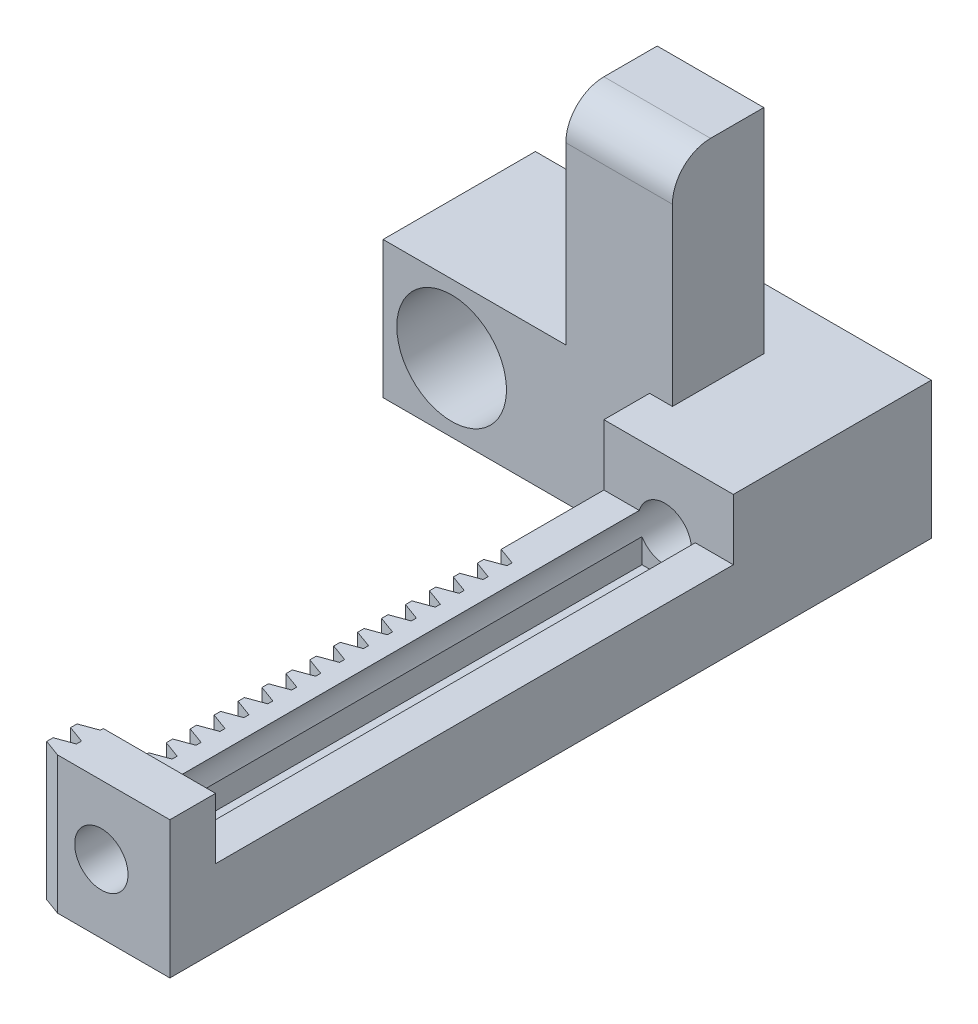
SolidWorks part; units mm, degrees
ref_plane "前视基准面" through (0, 0, 0) normal (0, 0, 1) x (1, 0, 0)
ref_plane "上视基准面" through (0, 0, 0) normal (0, 1, 0) x (1, 0, 0)
ref_plane "右视基准面" through (0, 0, 0) normal (1, 0, 0) x (0, 0, -1)
other "Configuration Table"
sketch "草图1" plane through (0, 0, 0) normal (0, 0, 1) x (1, 0, 0)
  line L1 (-13, 4.5) -> (13, 4.5)
  line L2 (-13, 4.5) -> (-13, -4.5)
  line L3 (-13, -4.5) -> (13, -4.5)
  line L4 (13, 4.5) -> (13, -4.5)
  line L5 (-13, 4.5) -> (13, -4.5) construction
  line L6 (-13, -4.5) -> (13, 4.5) construction
  point P0 (0, 0)
  dimension "D1" = 26
  dimension "D2" = 9
extrude "凸台-拉伸1" add sketch "草图1" against normal blind 10
sketch "草图2" plane through (0, 0, 0) normal (0, 0, 1) x (1, 0, 0)
  line L0 (0, 8.6502) -> (0, -9.0329) construction
  line L1 (8.5, 8.6502) -> (8.5, -9.0329) construction
  line L5 (-13, 0) -> (13, 0)
  line L6 (-13, 0) -> (13, 0) construction
  circle A0 centre (8.5, 0) radius 3.6
  circle A2 centre (-8.5, 0) radius 3.6
  dimension "D4" = 7.2
  dimension "D1" = 8.5
  dimension "D3" = 4.5
extrude "切除-拉伸1" cut sketch "草图2" against normal through all
sketch "草图5" plane through (-13, 0, 0) normal (-1, 0, 0) x (0, 0, 1)
  line L0 (0, 4.5) -> (-10, 4.5)
  line L1 (-10, 4.5) -> (-10, 8.3014)
  line L2 (-10, 8.3014) -> (-10, 30.5)
  line L3 (-9, 31.5) -> (-8, 31.5)
  line L4 (-8, 31.5) -> (-8, 20.1)
  line L5 (-6.4, 18.5) -> (-2.5, 18.5)
  line L6 (0, 16) -> (0, 4.5)
  line L7 (-10, 4.5) -> (-10, -4.5) construction
  arc A0 (-9, 31.5) -> (-10, 30.5) centre (-9, 30.5) ccw
  arc A1 (-6.4, 18.5) -> (-8, 20.1) centre (-6.4, 20.1) cw
  arc A2 (0, 16) -> (-2.5, 18.5) centre (-2.5, 16) ccw
  dimension "D4" = 1
  dimension "D5" = 1.6
  dimension "D6" = 2.5
  dimension "D1" = 27
  dimension "D2" = 14
  dimension "D3" = 8
extrude "凸台-拉伸2" add sketch "草图5" against normal through all
extrude "切除-拉伸2" cut sketch "草图5<2>" against normal blind 7
sketch "草图5<2>" plane through (-13, 0, 0) normal (-1, 0, 0) x (0, 0, 1) same geometry as "草图5"
mirror "镜向1" about plane through (0, 0, 0) normal (1, 0, 0) of "切除-拉伸2"
sketch "草图7" plane through (0, 0, 0) normal (0, 0, 1) x (1, 0, 0)
  line L0 (0, -9.5936) -> (0, 36.1115) construction
  line L2 (4.5, -4.5) -> (4.5, 4.5)
  line L3 (13, 4.5) -> (4.5, 4.5)
  line L4 (13, 4.5) -> (13, -4.5)
  line L5 (13, -4.5) -> (4.5, -4.5)
  line L6 (-13, -4.5) -> (13, -4.5) construction
  line L8 (4.5, -9.5936) -> (4.5, 36.1115) construction
  dimension "D1" = 4.5
extrude "凸台-拉伸3" add sketch "草图7" along normal blind 40
sketch "草图8" plane through (0, 0, 40) normal (0, 0, 1) x (1, 0, 0)
  circle A0 centre (8.5, 0) radius 1.75
  dimension "D1" = 3.5
extrude "切除-拉伸3" cut sketch "草图8" against normal blind 40
sketch "草图9" plane through (0, 4.5, 0) normal (0, 1, 0) x (1, 0, 0)
  line L2 (13, -40) -> (4.5, -40) construction
  line L3 (7, -3) -> (10.5, -3)
  line L5 (6, 10) -> (13, 10) construction
  line L6 (7, -37) -> (10.5, -37)
  line L7 (10.5, 10) -> (10.5, -40)
  line L8 (10.5, -3) -> (10.5, -37)
  line L11 (7, -40) -> (7, 0)
  line L12 (7, -37) -> (7, -3)
  dimension "D1" = 3
  dimension "D2" = 13
  dimension "D3" = 2.5
  dimension "D4" = 2.5
extrude "切除-拉伸4" cut sketch "草图9" against normal blind 7
sketch "草图10" plane through (0, 4.5, 0) normal (0, 1, 0) x (1, 0, 0)
  line L8 (5.625, -40) -> (5.625, -40.3304)
  line L9 (5.625, -40.3304) -> (4.5, -40.7399)
  line L10 (4.5, -40.7399) -> (4.5, -39.5905)
  line L11 (4.5, -39.5905) -> (5.625, -40)
  line L12 (5.625, -40.1652) -> (4.5, -40.1652) construction
  line L13 (5, -39.7725) -> (5, -40.5579) construction
  line L16 (4.5, -40) -> (4.5, 0) construction
  line L17 (13, -40) -> (4.5, -40) construction
  dimension "D1" = 0.625
  dimension "D2" = 0.7854
  dimension "D4" = 0.5
  dimension "D3" = 20
extrude "切除-拉伸12" cut sketch "草图10" against normal through all
pattern_linear "阵列(线性)2" count 20 spacing 1.5708 along (0, 0, -1) of "切除-拉伸12"
sketch "草图22" plane through (0, 4.5, 0) normal (0, 1, 0) x (1, 0, 0)
  line L0 (13, 10) -> (13, -40) construction
  line L5 (4.5, -3) -> (13, -3)
  line L6 (4.5, -3) -> (4.5, -37)
  line L11 (4.5, -37) -> (13, -37)
  line L12 (13, -37) -> (5.625, -37)
  line L13 (21.5249, -37) -> (-0.8919, -37) construction
  line L14 (13, -3) -> (13, -37)
  line L16 (4.5, -9.7454) -> (4.5, 0) construction
  line L17 (6, -3) -> (13, -3)
  line L18 (1.2536, -3) -> (17.4586, -3) construction
  dimension "D1" = 3
  dimension "D2" = 13
extrude "切除-拉伸13" cut sketch "草图22" against normal blind 4
sketch "草图23" plane through (0, 4.5, 0) normal (0, 1, 0) x (1, 0, 0)
  line L2 (0, 24.8411) -> (0, -13.0368) construction
  line L3 (6, 5) -> (13, 5)
  line L4 (3.4062, 5) -> (18.5675, 5) construction
  line L5 (8.5, 24.8411) -> (8.5, -13.0368) construction
  circle A0 centre (8.5, 5) radius 1.5
  circle A1 centre (-8.5, 5) radius 1.5
  dimension "D3" = 3
  dimension "D1" = 5
  dimension "D2" = 8.5
extrude "切除-拉伸14" [suppressed] cut sketch "草图23" against normal blind 4
sketch "草图27" plane through (-13, 0, 0) normal (-1, 0, 0) x (0, 0, 1)
  line L2 (-6, 4.5) -> (-6, -4.5)
  line L3 (-6, 36.3519) -> (-6, -12.2958) construction
  line L4 (-10, 4.5) -> (-6, 4.5)
  line L5 (-10, 4.5) -> (-10, 32.8452)
  line L6 (-10, 32.8452) -> (-6, 32.8452)
  line L7 (-6, 4.5) -> (-6, 32.8452)
  line L9 (-10, 4.5) -> (0, 4.5)
  line L10 (-10, 4.5) -> (0, 4.5) construction
  dimension "D1" = 4
  dimension "D2" = 9
extrude "切除-拉伸17" cut sketch "草图27" against normal through all both and the other way through all
extrude "切除-拉伸18" cut sketch "草图5<5>" against normal blind 12 and the other way through all
sketch "草图5<5>" plane through (-13, 0, 0) normal (-1, 0, 0) x (0, 0, 1) same geometry as "草图5"
sketch "草图28" plane through (0, 0, -6) normal (0, 0, -1) x (-1, 0, 0)
  line L2 (-6, 8.5) -> (1, 8.5)
  line L3 (-12.1246, 8.5) -> (6.8384, 8.5) construction
  line L7 (-2.5, 18.5) -> (-2.5, 4.5)
  line L8 (-2.5, 27.9683) -> (-2.5, 4.5) construction
  line L15 (-13, 13.5) -> (13, 13.5)
  line L16 (-11.8262, 13.5) -> (11.2052, 13.5) construction
  point P16 (-2.5, 8.5)
  point P44 (-2.5, 13.5)
  dimension "D1" = 4
  dimension "D2" = 3.5
  dimension "D3" = 9
hole_wizard "Ø2.0mm 暗销孔1" positions "草图28" profile "草图30" hole size "Ø2.0" standard "GB"
sketch "草图30" plane through (2.5, 13.5, -6) normal (1, 0, 0) x (0, 1, 0)
  line L0 (0, 0) -> (0, 5.4506)
  line L1 (0, 5.4506) -> (0.75, 5)
  line L2 (0.75, 5) -> (0.75, 0)
  line L5 (0.75, 0) -> (0, 0)
  line L10 (0, 5.4506) -> (-0.75, 5) construction
  line L11 (0, -6.35) -> (0, 107.95) construction
  dimension "孔直径" = 1.5
  dimension "孔深度" = 5
  dimension "导头角度" = 118
sketch "草图31" plane through (-1, 0, 0) normal (-1, 0, 0) x (0, 0, 1)
  line L2 (-10, 11) -> (0, 11)
  line L3 (-4.9342, 11) -> (-0.9742, 11) construction
  line L5 (-3, 8.6502) -> (-3, -9.0329)
  line L6 (-3, 13.1401) -> (-3, 9.1071) construction
  point P9 (-3, 11)
  dimension "D1" = 6.5
  dimension "D2" = 3
hole_wizard "Ø2.0mm 暗销孔2" positions "草图31" profile "草图32" hole size "Ø2.0" standard "GB"
sketch "草图32" plane through (-1, 11, -3) normal (0, 1, 0) x (0, 0, 1)
  line L0 (0, 0) -> (0, 4.4506)
  line L1 (0, 4.4506) -> (0.75, 4)
  line L2 (0.75, 4) -> (0.75, 0)
  line L5 (0.75, 0) -> (0, 0)
  line L10 (0, 4.4506) -> (-0.75, 4) construction
  line L11 (0, -6.35) -> (0, 107.95) construction
  dimension "孔直径" = 1.5
  dimension "孔深度" = 4
  dimension "导头角度" = 118
equation "\"m\"=0.5 '模数'"
equation "\"t\"=pi * \"m\" '周节'"
equation "\"S\"=pi / 2 * \"m\" '齿厚'"
equation "\"c\"=0.25 * \"m\" '径向间隙'"
equation "\"h1\"=\"m\" '齿顶高'"
equation "\"h2\"=1.25 * \"m\" '齿根高'"
equation "\"hg\"=2 * \"m\" '齿工作高度'"
equation "\"h\"=2.25 * \"m\" '齿全高'"
equation "\"D1@草图10\"=\"h2\""
equation "\"D2@草图10\"=\"S\""
equation "\"D4@草图10\"=\"m\""
equation "\"D3@阵列(线性)2\"=Pi*\"m\""
